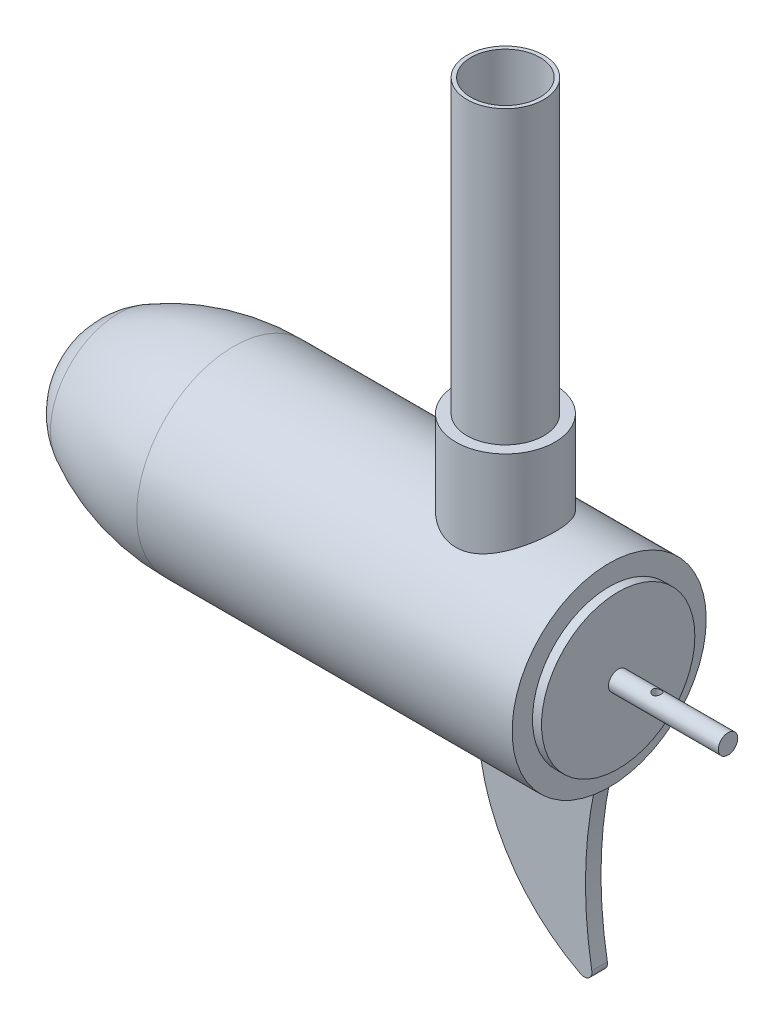
SolidWorks part; units mm, degrees
ref_plane "Front Plane" through (0, 0, 0) normal (0, 0, 1) x (1, 0, 0)
ref_plane "Top Plane" through (0, 0, 0) normal (0, 1, 0) x (1, 0, 0)
ref_plane "Right Plane" through (0, 0, 0) normal (1, 0, 0) x (0, 0, -1)
sketch "Sketch1" plane through (0, 0, 0) normal (0, 0, 1) x (1, 0, 0)
  line L0 (0, 0) -> (0, 31.75) construction
  line L1 (-88.9, 31.75) -> (0, 31.75)
  line L2 (0, 31.75) -> (38.1, 31.75)
  line L5 (38.1, 0) -> (0, 0)
  line L6 (0, 0) -> (-64.3283, 0)
  line L7 (-64.3283, 0) -> (-114.3, 0)
  line L8 (-114.3, 0) -> (-139.7, 0)
  line L9 (38.1, 31.75) -> (38.1, 0)
  circle A0 centre (-114.3, 0) radius 25.4
  arc A1 (-88.9, 31.75) -> (-126.5967, 22.225) centre (-88.9, -47.6079) ccw
  dimension "D1" = 50.8
  dimension "D2" = 38.1
  dimension "D3" = 139.7
  dimension "D4" = 31.75
  dimension "D5" = 88.9
  dimension "D6" = 22.225
revolve "Revolve1" add sketch "Sketch1" angle 360 about L6 region at (-49.1641, 16.5725, 0) region at (19.05, 15.875, 0) region at (-114.3, 10.7801, 0)
sketch "Sketch2" plane through (0, 0, 0) normal (0, 1, 0) x (1, 0, 0)
  circle A0 centre (0, 0) radius 12.573
  circle A1 centre (0, 0) radius 11.303
  dimension "D2" = 25.146
  dimension "D1" = 1.27
extrude "Boss-Extrude1" add sketch "Sketch2" along normal blind 635
sketch "Sketch4" plane through (0, 0, 0) normal (0, 0, 1) x (1, 0, 0)
  line L0 (-88.9, -31.75) -> (38.1, -31.75) construction
  line L1 (-6.35, -31.75) -> (31.75, -31.75) construction
  line L2 (12.7, -31.75) -> (12.7, -25.4) construction
  line L3 (-6.35, -31.75) -> (31.75, -31.75)
  line L4 (-6.35, -31.75) -> (-6.35, -25.4)
  line L5 (-6.35, -25.4) -> (31.75, -25.4)
  line L6 (31.75, -31.75) -> (31.75, -25.4)
  line L7 (-139.7, 0) -> (-139.7, -31.75) construction
  line L8 (-139.7, -31.75) -> (-6.35, -31.75) construction
  arc A0 (-6.35, -31.75) -> (31.75, -88.9) centre (55.5625, -31.75) ccw
  arc A1 (31.75, -31.75) -> (31.75, -88.9) centre (165.2511, -60.325) ccw
  arc A2 (-126.5967, 22.225) -> (-126.5967, -22.225) centre (-114.3, 0) ccw construction
  dimension "D3" = 136.525
  dimension "D1" = 38.1
  dimension "D2" = 88.9
  dimension "D5" = 6.35
  dimension "D6" = 171.45
extrude "Boss-Extrude3" add sketch "Sketch4" along normal blind 2.54 and the other way blind 2.54 contours A1 L3 A0 | L3 L6 L5 L4 region at (12.7, -28.575, 0) region at (14.8695, -53.9854, 0)
fillet "Fillet1" radius 2.54 1 edges at (31.75, -88.9, 0)
sketch "Sketch5" plane through (0, 0, 0) normal (0, 1, 0) x (1, 0, 0)
  circle A0 centre (0, 0) radius 16.1925
  dimension "D1" = 32.385
extrude "Boss-Extrude4" add sketch "Sketch5" along normal blind 57.15
sketch "Sketch6" plane through (0, 0, 0) normal (0, 0, 1) x (1, 0, 0)
  line L0 (12.573, 57.15) -> (12.573, 635) construction
  line L1 (-12.573, 635) -> (12.573, 635)
  line L2 (-12.573, 635) -> (-12.573, 279.4)
  line L3 (-12.573, 279.4) -> (12.573, 279.4)
  line L4 (12.573, 635) -> (12.573, 279.4)
  dimension "D1" = 355.6
extrude "Cut-Extrude1" cut sketch "Sketch6" against normal through all and the other way through all
sketch "Sketch7" plane through (38.1, 0, 0) normal (1, 0, 0) x (0, 0, -1)
  circle A0 centre (0, 0) radius 36.2779
extrude "Cut-Extrude2" cut sketch "Sketch7" against normal blind 4.158
sketch "Sketch8" plane through (33.942, 0, 0) normal (1, 0, 0) x (0, 0, -1)
  circle A0 centre (0, 0) radius 25.0825
  dimension "D1" = 50.165
extrude "Boss-Extrude5" add sketch "Sketch8" along normal blind 2.9464
sketch "Sketch9" plane through (36.8884, 0, 0) normal (1, 0, 0) x (0, 0, -1)
  circle A0 centre (0, 0) radius 3.175
  dimension "D1" = 6.35
extrude "Boss-Extrude6" add sketch "Sketch9" along normal blind 35.941
sketch "Sketch10" plane through (0, 0, 0) normal (0, 1, 0) x (1, 0, 0)
  line L0 (36.8884, -3.175) -> (36.8884, 3.175) construction
  circle A0 centre (49.5884, 0) radius 1.4224
  dimension "D2" = 2.8448
  dimension "D1" = 12.7
extrude "Cut-Extrude3" cut sketch "Sketch10" against normal through all and the other way through all
sketch "Sketch11" plane through (0, 279.4, 0) normal (0, 1, 0) x (1, 0, 0)
  circle A0 centre (0, 0) radius 17.1613
extrude "Cut-Extrude4" cut sketch "Sketch11" against normal blind 127
